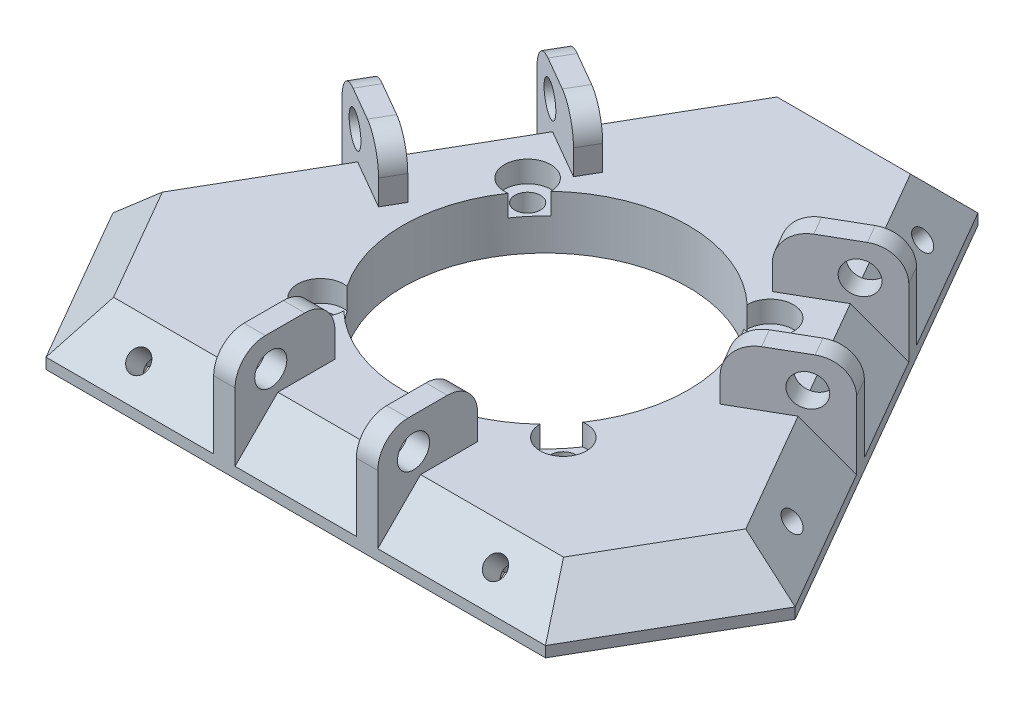
SolidWorks part; units mm, degrees
ref_plane "Front Plane" through (0, 0, 0) normal (0, 0, 1) x (1, 0, 0)
ref_plane "Top Plane" through (0, 0, 0) normal (0, 1, 0) x (1, 0, 0)
ref_plane "Right Plane" through (0, 0, 0) normal (1, 0, 0) x (0, 0, -1)
sketch "Sketch1" plane through (0, 42.8046, 0) normal (0, 1, 0) x (1, 0, 0)
  line L0 (72.8978, -65.2658) -> (37.8978, -4.6441)
  line L1 (68.3882, -77.4549) -> (25.0869, -2.4549) construction
  line L2 (25.0869, -2.4549) -> (-18.2144, -77.4549) construction
  line L3 (-18.2144, -77.4549) -> (68.3882, -77.4549) construction
  line L4 (12.276, -4.6441) -> (-22.724, -65.2658)
  line L5 (-9.9131, -87.4549) -> (60.0869, -87.4549)
  line L6 (7.276, -13.3043) -> (42.8978, -13.3043) construction
  line L7 (12.276, -4.6441) -> (37.8978, -4.6441)
  line L8 (72.8978, -65.2658) -> (60.0869, -87.4549)
  line L9 (67.8978, -56.6056) -> (50.0869, -87.4549) construction
  line L10 (-22.724, -65.2658) -> (-9.9131, -87.4549)
  line L11 (-17.724, -56.6056) -> (0.0869, -87.4549) construction
  line L12 (25.0869, 17.5451) -> (-35.5349, -87.4549) construction
  line L13 (85.7087, -87.4549) -> (25.0869, 17.5451) construction
  line L14 (-35.5349, -87.4549) -> (85.7087, -87.4549) construction
  line L15 (25.0869, -2.4549) -> (25.0869, -77.4549) construction
  line L16 (68.3882, -77.4549) -> (3.4363, -39.9549) construction
  line L17 (-18.2144, -77.4549) -> (46.7375, -39.9549) construction
  circle A0 centre (25.0869, -52.4549) radius 20
  circle A1 centre (25.0869, -52.4549) radius 25 construction
  dimension "D1" = 40
  dimension "D2" = 50
  dimension "D4" = 50
  dimension "D5" = 50
  dimension "D6" = 50
  dimension "D7" = 70
  dimension "D8" = 70
  dimension "D9" = 70
  dimension "D3" = 10
extrude "Boss-Extrude1" add sketch "Sketch1" along normal blind 7.5
chamfer "Chamfer2" distance 6 angle 45 6 edges at (55.3978, 50.3046, 34.9549) (66.4924, 50.3046, 76.3604) (25.0869, 50.3046, 87.4549) (-16.3185, 50.3046, 76.3604) (-5.224, 50.3046, 34.9549) (25.0869, 50.3046, 4.6441)
hole_wizard "CBORE for M3 SHCS1" positions "Sketch3" profile "Sketch2" counterbore size "M3" standard "ANSI Metric" end condition through all
sketch "Sketch3" plane through (0, 50.3046, 0) normal (0, 1, 0) x (1, 0, 0)
  point P0 (8.0869, -37.9549)
  point P2 (42.0869, -37.9549)
  point P4 (42.0869, -66.9549)
  point P6 (8.0869, -66.9549)
sketch "Sketch2" plane through (8.0869, 50.3046, 37.9549) normal (1, 0, 0) x (0, 0, 1)
  line L0 (0, 0) -> (0, 7.5)
  line L1 (0, 7.5) -> (1.8, 7.5)
  line L3 (1.8, 7.5) -> (1.8, 3)
  line L4 (1.8, 3) -> (3.25, 3)
  line L5 (3.25, 3) -> (3.25, 0)
  line L7 (3.25, 0) -> (0, 0)
  line L11 (0, -6.35) -> (0, 107.95) construction
  dimension "Thru Hole Dia." = 3.6
  dimension "Thru Hole Depth" = 7.5
  dimension "C'Bore Dia." = 6.5
  dimension "C'Bore Depth" = 3
sketch "Sketch4" plane through (0, 65.8798, 65.8798) normal (0, 0.7071, 0.7071) x (1, 0, 0)
  line L0 (25.0869, -22.0266) -> (25.0869, -30.5119) construction
  line L1 (-6.449, -22.0266) -> (56.6228, -22.0266) construction
  line L2 (60.0869, -30.5119) -> (-9.9131, -30.5119) construction
  line L3 (0.0869, -22.0266) -> (0.0869, -30.5119) construction
  circle A0 centre (0.0869, -26.2693) radius 1.5
  circle A1 centre (50.0869, -26.2693) radius 1.5
  dimension "D2" = 3
  dimension "D1" = 25
extrude "Cut-Extrude1" cut sketch "Sketch4" against normal up to next
sketch "Sketch5" plane through (0, 65.8798, 65.8798) normal (0, 0.7071, 0.7071) x (1, 0, 0)
  line L0 (25.0869, -22.0266) -> (25.0869, -30.5119) construction
  line L1 (3.2623, -26.2693) -> (1.6746, -23.5193)
  line L2 (1.6746, -23.5193) -> (-1.5008, -23.5193)
  line L3 (-1.5008, -23.5193) -> (-3.0885, -26.2693)
  line L4 (-3.0885, -26.2693) -> (-1.5008, -29.0193)
  line L5 (-1.5008, -29.0193) -> (1.6746, -29.0193)
  line L6 (1.6746, -29.0193) -> (3.2623, -26.2693)
  line L7 (-6.449, -22.0266) -> (56.6228, -22.0266) construction
  line L8 (60.0869, -30.5119) -> (-9.9131, -30.5119) construction
  line L9 (48.4992, -29.0193) -> (46.9115, -26.2693)
  line L10 (51.6746, -29.0193) -> (48.4992, -29.0193)
  line L11 (53.2623, -26.2693) -> (51.6746, -29.0193)
  line L12 (51.6746, -23.5193) -> (53.2623, -26.2693)
  line L13 (48.4992, -23.5193) -> (51.6746, -23.5193)
  line L14 (46.9115, -26.2693) -> (48.4992, -23.5193)
  circle A0 centre (0.0869, -26.2693) radius 2.75 construction
  circle A1 centre (50.0869, -26.2693) radius 2.75 construction
  dimension "D1" = 5.5
extrude "Cut-Extrude2" cut sketch "Sketch5" against normal blind 10 from offset 3.5 offset against normal yes
sketch "Sketch7" plane through (-13.5755, 15.6756, -7.8378) normal (-0.6124, 0.7071, -0.3536) x (0.7906, 0.5477, -0.2739)
  line L0 (17.1366, -56.4448) -> (10.5639, -51.0783) construction
  line L1 (37.0816, -32.0172) -> (-2.8085, -80.8724) construction
  line L2 (-11.5721, -78.1891) -> (32.6998, -23.9674) construction
  line L3 (32.9479, -37.0799) -> (26.3753, -31.7133) construction
  circle A0 centre (29.6616, -34.3966) radius 1.5
  circle A1 centre (-1.9612, -73.1265) radius 1.5
  dimension "D2" = 3
  dimension "D1" = 25
extrude "Cut-Extrude3" cut sketch "Sketch7" against normal blind 10
sketch "Sketch8" plane through (-13.5755, 15.6756, -7.8378) normal (-0.6124, 0.7071, -0.3536) x (0.7906, 0.5477, -0.2739)
  line L1 (32.7959, -34.906) -> (31.6699, -31.9369)
  line L2 (31.6699, -31.9369) -> (28.5356, -31.4275)
  line L3 (28.5356, -31.4275) -> (26.5273, -33.8872)
  line L4 (26.5273, -33.8872) -> (27.6533, -36.8563)
  line L5 (27.6533, -36.8563) -> (30.7876, -37.3657)
  line L6 (30.7876, -37.3657) -> (32.7959, -34.906)
  line L8 (-11.5721, -78.1891) -> (32.6998, -23.9674) construction
  line L9 (17.1366, -56.4448) -> (10.5639, -51.0783) construction
  line L10 (37.0816, -32.0172) -> (-2.8085, -80.8724) construction
  line L11 (1.1731, -73.6359) -> (-0.8352, -76.0955)
  line L12 (0.0471, -70.6668) -> (1.1731, -73.6359)
  line L13 (-3.0872, -70.1574) -> (0.0471, -70.6668)
  line L14 (-5.0955, -72.617) -> (-3.0872, -70.1574)
  line L15 (-3.9695, -75.5861) -> (-5.0955, -72.617)
  line L16 (-0.8352, -76.0955) -> (-3.9695, -75.5861)
  circle A0 centre (29.6616, -34.3966) radius 2.75 construction
  circle A1 centre (-1.9612, -73.1265) radius 2.75 construction
  dimension "D1" = 5.5
extrude "Cut-Extrude4" cut sketch "Sketch8" against normal blind 10 from offset 3.5 offset against normal yes
sketch "Sketch9" plane through (32.3906, 37.4015, -18.7007) normal (0.6124, 0.7071, -0.3536) x (0.7906, -0.5477, 0.2739)
  line L0 (22.5293, -56.4448) -> (29.102, -51.0783) construction
  line L1 (42.4744, -80.8724) -> (2.5843, -32.0172) construction
  line L2 (6.9661, -23.9674) -> (51.2379, -78.1891) construction
  line L3 (38.3407, -75.8097) -> (44.9134, -70.4432) construction
  circle A0 centre (41.6271, -73.1265) radius 1.5
  circle A1 centre (10.0043, -34.3966) radius 1.5
  dimension "D2" = 3
  dimension "D1" = 25
sketch "Sketch10" plane through (32.3906, 37.4015, -18.7007) normal (0.6124, 0.7071, -0.3536) x (0.7906, -0.5477, 0.2739)
  line L0 (6.9661, -23.9674) -> (51.2379, -78.1891) construction
  line L1 (39.6187, -70.6668) -> (38.4928, -73.6359)
  line L2 (38.4928, -73.6359) -> (40.5011, -76.0955)
  line L3 (40.5011, -76.0955) -> (43.6354, -75.5861)
  line L4 (43.6354, -75.5861) -> (44.7614, -72.617)
  line L5 (44.7614, -72.617) -> (42.753, -70.1574)
  line L6 (42.753, -70.1574) -> (39.6187, -70.6668)
  line L7 (22.5293, -56.4448) -> (29.102, -51.0783) construction
  line L8 (13.1386, -33.8872) -> (12.0126, -36.8563)
  line L9 (11.1303, -31.4275) -> (13.1386, -33.8872)
  line L10 (7.996, -31.9369) -> (11.1303, -31.4275)
  line L11 (6.87, -34.906) -> (7.996, -31.9369)
  line L12 (8.8783, -37.3657) -> (6.87, -34.906)
  line L13 (12.0126, -36.8563) -> (8.8783, -37.3657)
  circle A0 centre (41.6271, -73.1265) radius 2.75 construction
  circle A1 centre (10.0043, -34.3966) radius 2.75 construction
  dimension "D1" = 5.5
extrude "Cut-Extrude5" cut sketch "Sketch9" against normal blind 10
extrude "Cut-Extrude6" cut sketch "Sketch10" against normal blind 10 from offset 3.5 offset against normal yes
ref_plane "Plane1" through (28.9854, 0, 50.2042) normal (0.5, 0, 0.866) x (0.866, 0, -0.5)
ref_plane "Plane2" through (-16.4419, 0, 28.4783) normal (-0.5, 0, 0.866) x (0.866, 0, 0.5)
sketch "Sketch11" plane through (0, 42.8046, 0) normal (0, 1, 0) x (1, 0, 0)
  line L0 (25.0869, -52.4549) -> (25.0869, -87.4549) construction
  line L1 (-9.9131, -87.4549) -> (60.0869, -87.4549) construction
  line L2 (33.5869, -81.4549) -> (33.5869, -87.4549) construction
  line L3 (-6.449, -81.4549) -> (56.6228, -81.4549) construction
  line L4 (25.0869, -52.4549) -> (-5.224, -34.9549) construction
  line L5 (33.5869, -87.4549) -> (36.5869, -87.4549)
  line L6 (33.5869, -87.4549) -> (33.5869, -73.4549)
  line L7 (33.5869, -73.4549) -> (36.5869, -73.4549)
  line L8 (36.5869, -87.4549) -> (36.5869, -73.4549)
  line L9 (12.276, -4.6441) -> (-22.724, -65.2658) construction
  line L10 (25.0869, -52.4549) -> (55.3978, -34.9549) construction
  line L11 (72.8978, -65.2658) -> (37.8978, -4.6441) construction
  line L12 (46.4516, -31.4598) -> (51.6478, -28.4598) construction
  line L13 (65.9696, -65.2658) -> (34.4337, -10.6441) construction
  line L14 (-8.974, -41.4501) -> (-3.7778, -44.4501) construction
  line L15 (15.7401, -10.6441) -> (-15.7958, -65.2658) construction
  line L16 (16.5869, -81.4549) -> (16.5869, -87.4549) construction
  line L17 (13.5869, -87.4549) -> (13.5869, -73.4549)
  line L18 (16.5869, -73.4549) -> (13.5869, -73.4549)
  line L19 (16.5869, -87.4549) -> (16.5869, -73.4549)
  line L20 (16.5869, -87.4549) -> (13.5869, -87.4549)
  dimension "D1" = 8.5
  dimension "D2" = 3
  dimension "D3" = 14
  dimension "D4" = 7.5
  dimension "D5" = 7.5
extrude "Boss-Extrude2" add sketch "Sketch11" along normal blind 15.25
sketch "Sketch12" plane through (36.5869, 0, 0) normal (1, 0, 0) x (0, 0, -1)
  line L0 (-80.4549, 58.0546) -> (-80.4549, 42.8046) construction
  line L1 (-87.4549, 58.0546) -> (-73.4549, 58.0546) construction
  line L2 (-56.6056, 42.8046) -> (-87.4549, 42.8046) construction
  line L3 (-87.4549, 58.0546) -> (-87.4549, 44.3046) construction
  circle A0 centre (-82.4549, 53.6212) radius 2.25
  point P8 (-87.4549, 51.1796)
  dimension "D1" = 4.5
  dimension "D2" = 11
  dimension "D3" = 5
extrude "Cut-Extrude7" cut sketch "Sketch12" against normal through all both and the other way through all
fillet "Fillet1" radius 4.25 4 edges at (35.0869, 58.0546, 73.4549) (35.0869, 58.0546, 87.4549) (15.0869, 58.0546, 73.4549) (15.0869, 58.0546, 87.4549)
mirror "Mirror4" about plane through (28.9854, 0, 50.2042) normal (0.5, 0, 0.866) of "Fillet1", "Cut-Extrude7", "Boss-Extrude2"
mirror "Mirror5" about plane through (-16.4419, 0, 28.4783) normal (-0.5, 0, 0.866) of "Fillet1", "Cut-Extrude7", "Boss-Extrude2"
